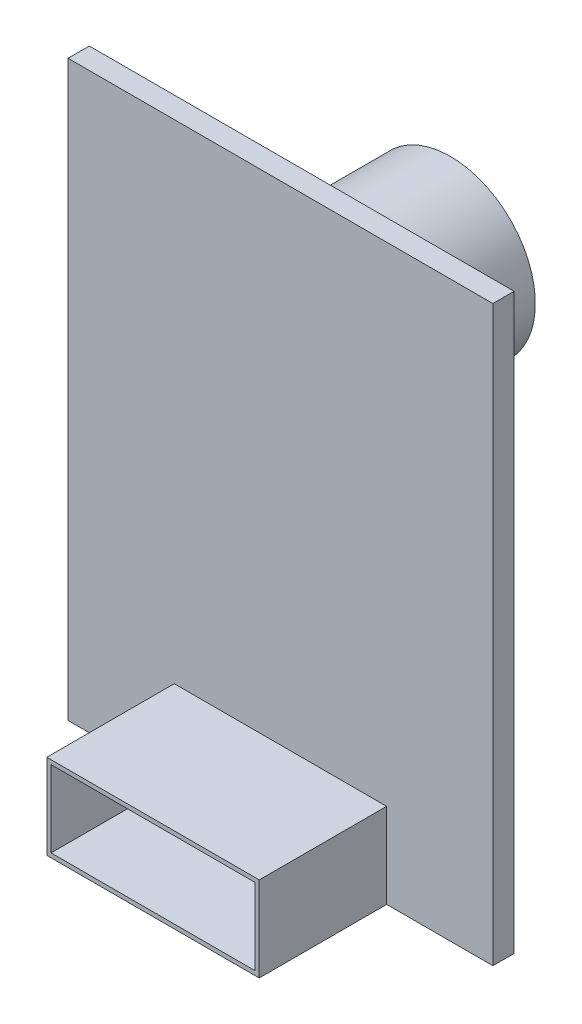
SolidWorks part; units mm, degrees
ref_plane "Front" through (0, 0, 0) normal (0, 0, 1) x (1, 0, 0)
ref_plane "Top" through (0, 0, 0) normal (0, 1, 0) x (1, 0, 0)
ref_plane "Right" through (0, 0, 0) normal (1, 0, 0) x (0, 0, -1)
sketch "Sketch1" plane through (0, 0, 0) normal (0, 0, 1) x (1, 0, 0)
  line L1 (-10, 13.5) -> (10, 13.5)
  line L2 (-10, 13.5) -> (-10, -13.5)
  line L3 (-10, -13.5) -> (10, -13.5)
  line L4 (10, 13.5) -> (10, -13.5)
  line L5 (-10, 13.5) -> (10, -13.5) construction
  line L6 (-10, -13.5) -> (10, 13.5) construction
  point P0 (0, 0)
  dimension "D1" = 20
  dimension "D2" = 27
extrude "Boss-Extrude1" add sketch "Sketch1" along normal blind 1
sketch "Sketch2" plane through (0, 0, 0) normal (0, 0, -1) x (-1, 0, 0)
  line L0 (-10, 13.5) -> (10, 13.5) construction
  line L1 (-4, 10.5) -> (4, 10.5)
  line L2 (-4, 10.5) -> (-4, 2.5)
  line L3 (-4, 2.5) -> (4, 2.5)
  line L4 (4, 10.5) -> (4, 2.5)
  line L5 (-4, 10.5) -> (4, 2.5) construction
  line L6 (-4, 2.5) -> (4, 10.5) construction
  line L7 (0, 6.5) -> (0, 0) construction
  circle A0 centre (0, 6.5) radius 4
  dimension "D1" = 8
  dimension "D2" = 7
extrude "Boss-Extrude2" add sketch "Sketch2" along normal blind 2 contours L1 L4 L3 L2
extrude "Boss-Extrude3" add sketch "Sketch2<3>" along normal blind 7 contours A0
sketch "Sketch2<3>" plane through (0, 0, 0) normal (0, 0, -1) x (-1, 0, 0) same geometry as "Sketch2"
sketch "Sketch3" plane through (0, 0, 1) normal (0, 0, 1) x (1, 0, 0)
  line L0 (-10, -13.5) -> (10, -13.5) construction
  line L1 (-5, -9.5) -> (5, -9.5)
  line L2 (-5, -9.5) -> (-5, -13.5)
  line L3 (-5, -13.5) -> (5, -13.5)
  line L4 (5, -9.5) -> (5, -13.5)
  line L5 (-5, -9.5) -> (5, -13.5) construction
  line L6 (-5, -13.5) -> (5, -9.5) construction
  line L7 (0, 0) -> (0, -11.5) construction
  point P0 (0, -11.5)
  point P9 (0, 0)
  dimension "D1" = 4
  dimension "D2" = 10
extrude "Extrude-Thin1" add sketch "Sketch3" along normal blind 6 thin thin type one direction reverse wall 0.2
